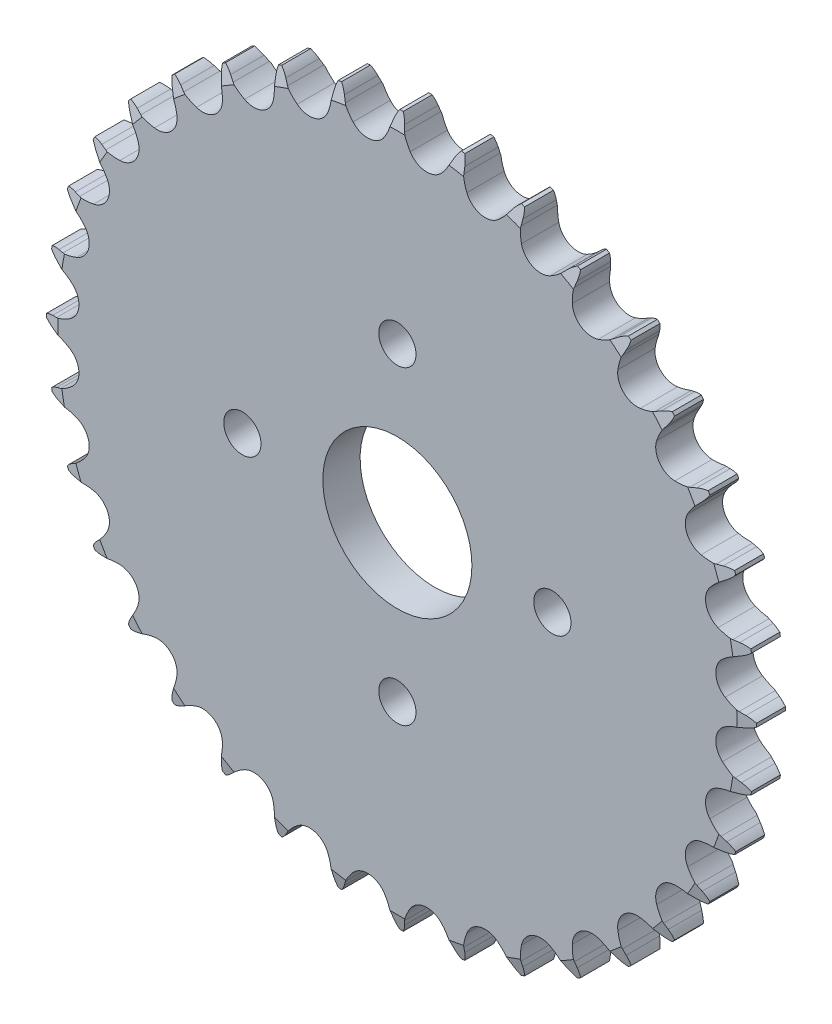
SolidWorks part; units mm, degrees
ref_plane "Front Plane" through (0, 0, 0) normal (0, 0, 1) x (1, 0, 0)
ref_plane "Top Plane" through (0, 0, 0) normal (0, 1, 0) x (1, 0, 0)
ref_plane "Right Plane" through (0, 0, 0) normal (1, 0, 0) x (0, 0, -1)
sketch "Sketch1" plane through (0, 0, 0) normal (0, 0, 1) x (1, 0, 0)
  line L3 (0, 0) -> (0, 54.4723) construction
  line L4 (-44.2979, 54.6436) -> (42.9505, 54.6436) construction
  line L5 (4.0748, 39.4826) -> (4.0748, 22.7186) construction
  line L6 (-19.6613, 57.6771) -> (20.7308, 57.6771) construction
  line L7 (4.0748, 57.6771) -> (-8.9514, 47.9795) construction
  line L8 (4.0748, 57.6771) -> (-3.6877, 54.8177) construction
  line L9 (-3.6877, 54.8177) -> (-6.0937, 61.3491) construction
  line L10 (-8.8562, 36.9773) -> (-8.8562, 20.618) construction
  line L11 (-19.962, 53.8687) -> (23.9482, 53.8687) construction
  line L12 (0, 0) -> (-3.9397, 45.0315) construction
  line L13 (-3.6877, 54.8177) -> (-3.9974, 55.6586) construction
  line L14 (3.6877, 54.8177) -> (3.9974, 55.6586) construction
  line L59 (0, 0) -> (0, -36) construction
  circle A0 centre (0, 0) radius 6 construction
  circle A2 centre (0, 0) radius 57.15 construction
  circle A8 centre (0, 0) radius 54.6436 construction
  circle A9 centre (0, 54.6436) radius 3.1781 construction
  arc A10 (-3.6877, 54.8177) -> (-2.5492, 52.7457) centre (4.0572, 57.7245) ccw construction
  circle A11 centre (-8.8562, 53.8687) radius 5.1779 construction
  arc A12 (2.5492, 52.7457) -> (-2.5492, 52.7457) centre (0, 54.6436) cw construction
  arc A13 (-2.5492, 52.7457) -> (-3.6877, 54.8177) centre (4.0572, 57.7245) cw construction
  arc A14 (-3.9974, 55.6586) -> (-5.0169, 57.343) centre (-8.8562, 53.8687) ccw construction
  arc A15 (2.5492, 52.7457) -> (3.6877, 54.8177) centre (-4.0572, 57.7245) ccw construction
  arc A16 (3.9974, 55.6586) -> (5.0169, 57.343) centre (8.8562, 53.8687) cw construction
  arc A127 (-5.0169, 57.343) -> (5.0169, 57.343) centre (0, 54.6436) cw construction
  point P24 (4.0748, 57.6771)
  point P27 (0, 54.6436)
  point P38 (-5.0169, 57.343)
  point P339 (0, 0)
sketch "Sketch2" plane through (0, 0, 0) normal (1, 0, 0) x (0, 0, -1)
  line L1 (-3, 6) -> (3, 6) construction
  line L3 (-3, -57.15) -> (3, -57.15) construction
  line L4 (-3, 57.15) -> (3, 57.15) construction
  line L11 (-3, 0) -> (3, 0) construction
  point P4 (0, 6)
  point P6 (0, 57.15)
  point P10 (0, -57.15)
  point P14 (0, 0)
  dimension "O'all Width" = 6
sketch "Sketch3" plane through (0, 0, 0) normal (1, 0, 0) x (0, 0, -1)
  line L0 (-3, 57.15) -> (3, 57.15) construction
  line L1 (-3, 6) -> (3, 6)
  line L2 (-3, 6) -> (-3, 57.15)
  line L3 (-3, 57.15) -> (3, 57.15)
  line L4 (3, 6) -> (3, 57.15)
  line L5 (-3, 6) -> (3, 6) construction
revolve "Revolve5" add sketch "Sketch3" angle 360 about L11
sketch "Sketch4" plane through (0, 0, 0) normal (0, 0, 1) x (1, 0, 0)
  line L0 (-3.6877, 54.8177) -> (-3.9974, 55.6586) construction
  line L1 (1.104, 54.9305) -> (0.8687, 55.7952)
  line L2 (-3.6877, 54.8177) -> (-3.9974, 55.6586) construction
  line L4 (3.6877, 54.8177) -> (3.9974, 55.6586) construction
  line L5 (3.6877, 54.8177) -> (3.9974, 55.6586) construction
  line L6 (0, 0) -> (0, 57.15) construction
  line L9 (8.4513, 54.2877) -> (8.8332, 55.0984)
  line L10 (0, 0) -> (4.7625, 54.4356) construction
  line L11 (0, 0) -> (-4.7625, 54.4356) construction
  arc A0 (-3.9974, 55.6586) -> (-5.0169, 57.343) centre (-8.8562, 53.8687) ccw construction
  arc A1 (-3.6877, 54.8177) -> (-2.5492, 52.7457) centre (4.0572, 57.7245) ccw construction
  arc A2 (-2.5492, 52.7457) -> (2.5492, 52.7457) centre (0, 54.6436) ccw construction
  circle A3 centre (0, 0) radius 57.15 construction
  arc A6 (-3.9974, 55.6586) -> (-5.0169, 57.343) centre (-8.8562, 53.8687) ccw construction
  arc A7 (-3.6877, 54.8177) -> (-2.5492, 52.7457) centre (4.0572, 57.7245) ccw construction
  arc A8 (-2.5492, 52.7457) -> (2.5492, 52.7457) centre (0, 54.6436) ccw construction
  arc A12 (2.5492, 52.7457) -> (3.6877, 54.8177) centre (-4.0572, 57.7245) ccw construction
  arc A13 (5.0169, 57.343) -> (3.9974, 55.6586) centre (8.8562, 53.8687) ccw construction
  arc A14 (5.0169, 57.343) -> (-5.0169, 57.343) centre (0, 54.6436) ccw construction
  arc A15 (2.5492, 52.7457) -> (3.6877, 54.8177) centre (-4.0572, 57.7245) ccw construction
  arc A16 (5.0169, 57.343) -> (3.9974, 55.6586) centre (8.8562, 53.8687) ccw construction
  arc A17 (5.0169, 57.343) -> (-5.0169, 57.343) centre (0, 54.6436) ccw construction
  arc A23 (9.9955, 56.6876) -> (0, 57.5621) centre (4.7625, 54.4356) ccw
  arc A24 (0.8687, 55.7952) -> (0, 57.5621) centre (-4.1275, 54.4356) ccw
  arc A25 (1.104, 54.9305) -> (2.0576, 52.7672) centre (9.0728, 57.1512) ccw
  arc A26 (2.0576, 52.7672) -> (7.1366, 52.3228) centre (4.7625, 54.4356) ccw
  arc A27 (7.1366, 52.3228) -> (8.4513, 54.2877) centre (0.9893, 57.8584) ccw
  arc A28 (9.9955, 56.6876) -> (8.8332, 55.0984) centre (13.5174, 52.8919) ccw
  circle A29 centre (0, 0) radius 54.6436 construction
  circle A30 centre (0, 0) radius 60.3406 construction
  dimension "D2" = 5
  dimension "D4" = 20.222
  dimension "D5" = 20.222
  dimension "D1" = 5
  dimension "D3" = 2
extrude "Cut-Extrude4" cut sketch "Sketch4" against normal through all both and the other way through all
pattern_circular "CirPattern2" count 36 over 360 about axis through (0, 0, 3) along (0, 0, -1) of "Cut-Extrude4"
sketch "Sketch5" plane through (0, 0, 3) normal (0, 0, 1) x (1, 0, 0)
  circle A0 centre (0, 0) radius 54.6436 construction
  circle A1 centre (0, 0) radius 54.6436
extrude "Cut-Extrude5" cut sketch "Sketch5" against normal through all draft 75 flip side to cut
sketch "Sketch6" plane through (0, 0, -3) normal (0, 0, -1) x (-1, 0, 0)
  circle A1 centre (0, 0) radius 54.6436
  circle A2 centre (0, 0) radius 54.6436
  dimension "D1" = 0
extrude "Cut-Extrude6" cut sketch "Sketch6" against normal through all draft 75 flip side to cut
sketch "Sketch7" plane through (0, 0, 0) normal (0, 0, 1) x (1, 0, 0)
  point P0 (4.7625, 54.4356)
  point P1 (-4.7625, 54.4356)
ref_axis "Center Axis 1" through (0, 0, -3) along (0, 0, 1)
ref_axis "Center Axis 2" through (4.7625, 54.4356, -21.9306) along (0, 0, 1)
ref_axis "Center Axis 3" through (-4.7625, 54.4356, -22.0643) along (0, 0, 1)
sketch "Sketch8" plane through (0, 0, 3) normal (0, 0, 1) x (1, 0, 0)
  circle A0 centre (0, 0) radius 12
  circle A1 centre (0, 24.95) radius 3
  circle A2 centre (-24.95, 0) radius 3
  circle A3 centre (24.95, 0) radius 3
  circle A4 centre (0, -24.95) radius 3
extrude "Cut-Extrude7" cut sketch "Sketch8" against normal blind 63
equation "\"D1@Sketch1\"=\"E@Sketch1\""
equation "\"No. of Teeth@CirPattern2\"=\"No. of Teeth@Sketch1\""
equation "\"D2@Sketch4\" =  ( 360 / \"No. of Teeth@Sketch1\" )  * .5"
equation "\"D5@Sketch4\" = \"D4@Sketch4\""
equation "\"D1@Sketch4\" = \"D2@Sketch4\""
